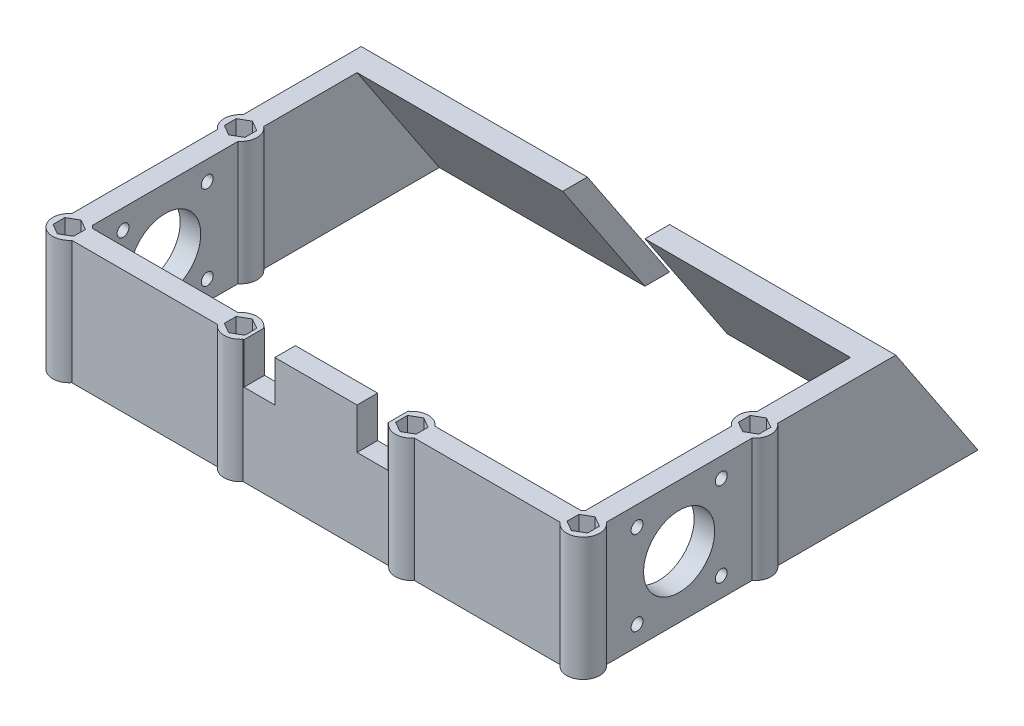
SolidWorks part; units mm, degrees
material "Custom Plastic"
ref_plane "Front Plane" through (0, 0, 0) normal (0, 0, 1) x (1, 0, 0)
ref_plane "Top Plane" through (0, 0, 0) normal (0, 1, 0) x (1, 0, 0)
ref_plane "Right Plane" through (0, 0, 0) normal (1, 0, 0) x (0, 0, -1)
sketch "Sketch4" plane through (0, 0, 0) normal (0, 1, 0) x (1, 0, 0)
  line L0 (0, 0) -> (0, -54.2428)
  line L1 (0, -114.3) -> (52.1261, -114.3) construction
  line L2 (165.1, -107.1594) -> (165.1, -62.1739)
  line L3 (165.1, 0) -> (158.75, 0)
  line L4 (158.75, 0) -> (158.75, -54.2428)
  line L7 (6.35, 0) -> (0, 0)
  line L8 (3.175, -111.125) -> (56.0917, -111.125) construction
  line L9 (56.0917, -111.125) -> (109.0083, -111.125) construction
  line L10 (109.0083, -111.125) -> (161.925, -111.125) construction
  line L11 (161.925, -111.125) -> (161.925, -58.2083) construction
  line L12 (6.35, -107.1594) -> (6.35, -62.1739)
  line L13 (6.35, -54.2428) -> (6.35, 0)
  line L14 (0, -62.1739) -> (0, -114.3) construction
  line L15 (0, -62.1739) -> (0, -107.1594)
  line L16 (7.1406, -114.3) -> (52.1261, -114.3)
  line L17 (52.1261, -107.95) -> (7.1406, -107.95)
  line L18 (60.0572, -114.3) -> (105.0428, -114.3) construction
  line L19 (60.0572, -114.3) -> (105.0428, -114.3)
  line L20 (105.0428, -107.95) -> (60.0572, -107.95)
  line L21 (112.9739, -114.3) -> (165.1, -114.3) construction
  line L22 (112.9739, -114.3) -> (157.9594, -114.3)
  line L23 (158.75, -62.1739) -> (158.75, -107.1594)
  line L24 (165.1, -54.2428) -> (165.1, 0)
  line L26 (157.9594, -107.95) -> (112.9739, -107.95)
  line L27 (0, -56.3752) -> (0, -60.0414)
  line L28 (0, -60.0414) -> (3.175, -61.8745)
  line L29 (3.175, -61.8745) -> (6.35, -60.0414)
  line L30 (6.35, -60.0414) -> (6.35, -56.3752)
  line L31 (6.35, -56.3752) -> (3.175, -54.5422)
  line L32 (3.175, -54.5422) -> (0, -56.3752)
  line L33 (3.175, -107.4588) -> (0, -109.2919)
  line L34 (0, -109.2919) -> (0, -112.9581)
  line L35 (0, -112.9581) -> (3.175, -114.7912)
  line L36 (3.175, -114.7912) -> (6.35, -112.9581)
  line L37 (6.35, -112.9581) -> (6.35, -109.2919)
  line L38 (6.35, -109.2919) -> (3.175, -107.4588)
  line L39 (56.0917, -107.4588) -> (52.9167, -109.2919)
  line L40 (52.9167, -109.2919) -> (52.9167, -112.9581)
  line L41 (52.9167, -112.9581) -> (56.0917, -114.7912)
  line L42 (56.0917, -114.7912) -> (59.2667, -112.9581)
  line L43 (59.2667, -112.9581) -> (59.2667, -109.2919)
  line L44 (59.2667, -109.2919) -> (56.0917, -107.4588)
  line L45 (109.0083, -107.4588) -> (105.8333, -109.2919)
  line L46 (105.8333, -109.2919) -> (105.8333, -112.9581)
  line L47 (105.8333, -112.9581) -> (109.0083, -114.7912)
  line L48 (109.0083, -114.7912) -> (112.1833, -112.9581)
  line L49 (112.1833, -112.9581) -> (112.1833, -109.2919)
  line L50 (112.1833, -109.2919) -> (109.0083, -107.4588)
  line L51 (161.925, -107.4588) -> (158.75, -109.2919)
  line L52 (158.75, -109.2919) -> (158.75, -112.9581)
  line L53 (158.75, -112.9581) -> (161.925, -114.7912)
  line L54 (161.925, -114.7912) -> (165.1, -112.9581)
  line L55 (165.1, -112.9581) -> (165.1, -109.2919)
  line L56 (165.1, -109.2919) -> (161.925, -107.4588)
  line L57 (161.925, -54.5422) -> (158.75, -56.3752)
  line L58 (158.75, -56.3752) -> (158.75, -60.0414)
  line L59 (158.75, -60.0414) -> (161.925, -61.8745)
  line L60 (161.925, -61.8745) -> (165.1, -60.0414)
  line L61 (165.1, -60.0414) -> (165.1, -56.3752)
  line L62 (165.1, -56.3752) -> (161.925, -54.5422)
  arc A6 (0, -54.2428) -> (0, -62.1739) centre (3.175, -58.2083) ccw
  arc A7 (6.35, -62.1739) -> (6.35, -54.2428) centre (3.175, -58.2083) ccw
  arc A8 (0, -107.1594) -> (7.1406, -114.3) centre (3.175, -111.125) ccw
  arc A9 (60.0572, -107.95) -> (52.1261, -107.95) centre (56.0917, -111.125) ccw
  arc A10 (52.1261, -114.3) -> (60.0572, -114.3) centre (56.0917, -111.125) ccw
  arc A11 (105.0428, -114.3) -> (112.9739, -114.3) centre (109.0083, -111.125) ccw
  arc A12 (112.9739, -107.95) -> (105.0428, -107.95) centre (109.0083, -111.125) ccw
  arc A13 (157.9594, -114.3) -> (165.1, -107.1594) centre (161.925, -111.125) ccw
  arc A14 (158.75, -54.2428) -> (158.75, -62.1739) centre (161.925, -58.2083) ccw
  arc A15 (165.1, -62.1739) -> (165.1, -54.2428) centre (161.925, -58.2083) ccw
  arc A16 (6.35, -107.1594) -> (7.1406, -107.95) centre (3.175, -111.125) cw
  arc A17 (158.75, -107.1594) -> (157.9594, -107.95) centre (161.925, -111.125) ccw
  circle A18 centre (3.175, -58.2083) radius 3.175 construction
  circle A19 centre (3.175, -111.125) radius 3.175 construction
  circle A20 centre (56.0917, -111.125) radius 3.175 construction
  circle A21 centre (109.0083, -111.125) radius 3.175 construction
  circle A22 centre (161.925, -111.125) radius 3.175 construction
  circle A23 centre (161.925, -58.2083) radius 3.175 construction
  point P7 (0, 0)
  point P30 (161.925, 0)
  point P51 (3.175, 0)
  dimension "D6" = 6.35
  dimension "D8" = 5.08
  dimension "D10" = 10.16
  dimension "D11" = 5.08
  dimension "D12" = 5.08
  dimension "D13" = 10.16
  dimension "D14" = 10.16
  dimension "D15" = 6.35
  dimension "D16" = 6.35
  dimension "D17" = 6.35
  dimension "D18" = 6.35
  dimension "D19" = 6.35
  dimension "D2" = 6.35
  dimension "D3" = 6.35
  dimension "D4" = 165.1
  dimension "D5" = 114.3
  dimension "D7" = 3.175
  dimension "D9" = 6.35
extrude "Boss-Extrude2" add sketch "Sketch4" along normal blind 38.1
chamfer "Chamfer2" distance 38.1 distance2 25.4 2 edges at (161.925, 38.1, 0) (3.175, 38.1, 0) first distance on face at (161.925, 19.05, 0) first distance on face at (3.175, 19.05, 0)
sketch "Sketch6" plane through (0, 0, 114.3) normal (0, 0, 1) x (1, 0, 0)
  line L0 (60.325, 38.1) -> (60.325, 25.4)
  line L1 (60.0572, 38.1) -> (105.0428, 38.1) construction
  line L2 (60.325, 25.4) -> (69.85, 25.4)
  line L3 (69.85, 25.4) -> (69.85, 38.1)
  line L4 (95.25, 38.1) -> (95.25, 25.4)
  line L5 (95.25, 25.4) -> (104.775, 25.4)
  line L6 (104.775, 25.4) -> (104.775, 38.1)
  line L7 (95.25, 38.1) -> (104.775, 38.1)
  line L8 (60.325, 38.1) -> (69.85, 38.1)
  line L9 (60.0572, 38.1) -> (60.325, 38.1) construction
  line L10 (104.775, 38.1) -> (105.0428, 38.1) construction
  dimension "D1" = 9.525
  dimension "D2" = 9.525
  dimension "D3" = 12.7
  dimension "D4" = 12.7
  dimension "D5" = 25.4
extrude "Cut-Extrude3" cut sketch "Sketch6" against normal through all
sketch "Sketch7" plane through (165.1, 0, 0) normal (1, 0, 0) x (0, 0, -1)
  line L0 (-71.6667, 32.05) -> (-97.6667, 6.05) construction
  line L1 (-71.6667, 32.05) -> (-71.6667, 6.05) construction
  line L2 (-71.6667, 6.05) -> (-97.6667, 6.05) construction
  line L3 (-97.6667, 6.05) -> (-97.6667, 32.05) construction
  line L4 (-97.6667, 32.05) -> (-71.6667, 32.05) construction
  line L6 (-116.205, 38.1) -> (-116.205, 0) construction
  line L7 (-116.205, 19.05) -> (-84.6667, 19.05) construction
  line L8 (-84.6667, 19.05) -> (-84.6667, 38.1) construction
  line L9 (-107.1594, 38.1) -> (-62.1739, 38.1) construction
  circle A0 centre (-84.6667, 19.05) radius 10.9855
  circle A1 centre (-71.6667, 32.05) radius 1.8415
  circle A2 centre (-71.6667, 6.05) radius 1.8415
  circle A3 centre (-97.6667, 6.05) radius 1.8415
  circle A4 centre (-97.6667, 32.05) radius 1.8415
  dimension "D2" = 21.971
  dimension "D3" = 3.683
  dimension "D1" = 26
extrude "Cut-Extrude4" cut sketch "Sketch7" against normal through all
sketch "Sketch8" plane through (0, 0, 0) normal (0, 0.5547, -0.8321) x (-1, 0, 0)
  line L0 (-165.1, 45.7905) -> (-95.25, 45.7905)
  line L1 (-95.25, 45.7905) -> (-95.25, 0)
  line L2 (-95.25, 0) -> (-165.1, 0)
  line L3 (-165.1, 0) -> (-165.1, 45.7905)
  line L4 (-69.85, 45.7905) -> (0, 45.7905)
  line L5 (0, 45.7905) -> (0, 0)
  line L6 (0, 0) -> (-69.85, 0)
  line L7 (-69.85, 0) -> (-69.85, 45.7905)
  point P3 (-63.2499, 45.1653)
  point P14 (0, 0)
  point P15 (0, 0)
extrude "Boss-Extrude3" add sketch "Sketch8" along normal blind 6.35
sketch "Sketch9" plane through (165.1, 0, 0) normal (1, 0, 0) x (0, 0, -1)
  line L0 (-25.4, 38.1) -> (-17.7682, 38.1)
  line L1 (-20.1165, 41.6223) -> (5.2835, 3.5223) construction
  line L2 (-17.7682, 38.1) -> (-20.1165, 41.6223)
  line L3 (-20.1165, 41.6223) -> (-25.4, 38.1)
extrude "Cut-Extrude5" cut sketch "Sketch9" against normal through all and the other way through all
sketch "Sketch10" plane through (165.1, 0, 0) normal (1, 0, 0) x (0, 0, -1)
  line L0 (0, 0) -> (7.6318, 0)
  line L1 (7.6318, 0) -> (5.2835, 3.5223)
  line L2 (-17.7682, 38.1) -> (5.2835, 3.5223) construction
  line L3 (5.2835, 3.5223) -> (0, 0)
extrude "Boss-Extrude4" add sketch "Sketch10" against normal up to surface (69.85 mm away) up to face at (95.25, 19.9306, 9.4712)
sketch "Sketch11" plane through (0, 0, 0) normal (-1, 0, 0) x (0, 0, 1)
  line L0 (-5.2835, 3.5223) -> (-7.6318, 0)
  line L1 (-7.6318, 0) -> (0, 0)
  line L2 (0, 0) -> (-5.2835, 3.5223)
extrude "Boss-Extrude5" add sketch "Sketch11" against normal up to surface (69.85 mm away) up to face at (69.85, 19.9306, 9.4712)
